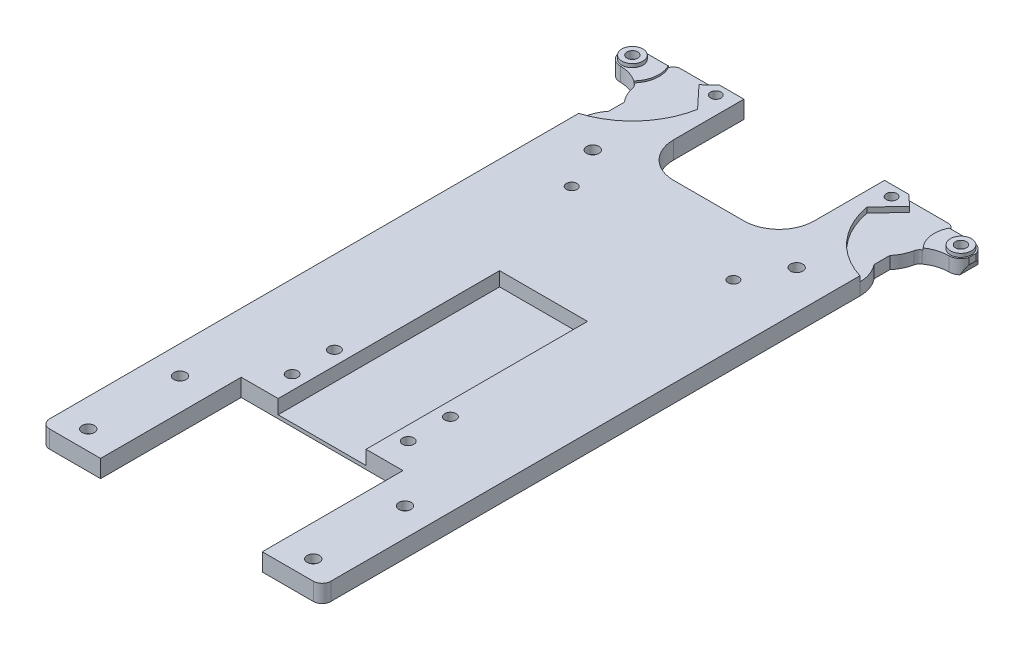
SolidWorks part; units mm, degrees
ref_plane "Front Plane" through (0, 0, 0) normal (0, 0, 1) x (1, 0, 0)
ref_plane "Top Plane" through (0, 0, 0) normal (0, 1, 0) x (1, 0, 0)
ref_plane "Right Plane" through (0, 0, 0) normal (1, 0, 0) x (0, 0, -1)
sketch "Sketch2" plane through (0, 0, 0) normal (0, 1, 0) x (1, 0, 0)
  line L0 (-93.7173, 35.2574) -> (6.2827, 35.2574)
  line L1 (6.2827, 35.2574) -> (6.2827, 25.2574)
  line L2 (6.2827, 25.2574) -> (-3.7173, 25.2574)
  line L3 (-3.7173, 25.2574) -> (-3.7173, -134.7426)
  line L4 (-3.7173, -134.7426) -> (6.2827, -134.7426)
  line L5 (6.2827, -134.7426) -> (6.2827, -144.7426)
  line L6 (6.2827, -144.7426) -> (-93.7173, -144.7426)
  line L7 (-93.7173, -144.7426) -> (-93.7173, -134.7426)
  line L8 (-93.7173, -134.7426) -> (-83.7173, -134.7426)
  line L9 (-83.7173, -134.7426) -> (-83.7173, 25.2574)
  line L10 (-83.7173, 25.2574) -> (-93.7173, 25.2574)
  line L11 (-93.7173, 25.2574) -> (-93.7173, 35.2574)
  line L12 (-43.7173, 35.2574) -> (-43.7173, -144.7426) construction
  line L13 (-83.7173, -54.7426) -> (-3.7173, -54.7426) construction
  circle A4 centre (-82.9402, 30.2574) radius 1.5
  circle A5 centre (-4.4944, 30.2574) radius 1.5
  circle A6 centre (-4.4944, -139.7426) radius 1.5
  circle A7 centre (-82.9402, -139.7426) radius 1.5
  circle A8 centre (-68.7173, 32.2574) radius 1.5
  circle A9 centre (-18.7173, 32.2574) radius 1.5
  circle A10 centre (-66.7173, -10.7426) radius 1.5
  circle A11 centre (-20.7173, -10.7426) radius 1.5
  dimension "D6" = 3
  dimension "D7" = 3
  dimension "D8" = 3
  dimension "D13" = 17
  dimension "D1" = 180
  dimension "D2" = 100
  dimension "D3" = 10
  dimension "D4" = 10
  dimension "D5" = 10
  dimension "D9" = 25
  dimension "D10" = 10
  dimension "D11" = 10.7771
  dimension "D12" = 5
  dimension "D14" = 46
extrude "Boss-Extrude1" add sketch "Sketch2" along normal blind 5
sketch "Sketch3" plane through (0, 5, 0) normal (0, 1, 0) x (1, 0, 0)
  line L0 (-93.7173, 35.2574) -> (-93.7173, 25.2574) construction
  line L1 (-93.7173, 33.6874) -> (-83.7173, 33.6874)
  line L2 (-93.7173, 33.6874) -> (-93.7173, 35.2574)
  line L3 (-93.7173, 35.2574) -> (-83.7173, 35.2574)
  line L4 (-83.7173, 33.6874) -> (-83.7173, 35.2574)
  line L5 (-88.7173, 35.2574) -> (-88.7173, 33.6874) construction
  line L6 (-93.7173, 34.4724) -> (-83.7173, 34.4724) construction
  line L7 (6.2827, 35.2574) -> (-93.7173, 35.2574) construction
  line L8 (-83.7173, 25.2574) -> (-83.7173, -134.7426) construction
  line L9 (-43.7173, 35.2574) -> (-43.7173, 20.5775) construction
  line L10 (6.2827, 35.2574) -> (-3.7173, 35.2574)
  line L11 (-3.7173, 33.6874) -> (-3.7173, 35.2574)
  line L12 (6.2827, 33.6874) -> (-3.7173, 33.6874)
  line L13 (6.2827, 33.6874) -> (6.2827, 35.2574)
  circle A0 centre (-82.9402, 30.2574) radius 1.5 construction
  point P404 (-88.7173, 34.4724)
  dimension "D1" = 3.43
extrude "Cut-Extrude1" cut sketch "Sketch3" against normal blind 10
fillet "Fillet1" radius 2 6 edges at (-93.7173, 2.5, -33.6874) (-83.7173, 2.5, -35.2574) (6.2827, 2.5, -25.2574) (6.2827, 2.5, -33.6874) (-3.7173, 2.5, -35.2574) (-93.7173, 2.5, -25.2574)
fillet "Fillet2" radius 2 8 edges at (-83.7173, 2.5, -25.2574) (-3.7173, 2.5, -25.2574) (-3.7173, 2.5, 134.7426) (-83.7173, 2.5, 134.7426) (-93.7173, 2.5, 134.7426) (-93.7173, 2.5, 144.7426) (6.2827, 2.5, 144.7426) (6.2827, 2.5, 134.7426)
sketch "Sketch30" plane through (0, 5, 0) normal (0, 1, 0) x (1, 0, 0)
  line L0 (-63.7173, 35.2574) -> (-63.7173, 5.2574)
  line L1 (-5.6705, 35.2574) -> (-81.7641, 35.2574) construction
  line L2 (-63.7173, 5.2574) -> (-23.7173, 5.2574)
  line L3 (-23.7173, 5.2574) -> (-23.7173, 35.2574)
  line L4 (-23.7173, 35.2574) -> (-63.7173, 35.2574)
  line L5 (-83.7173, 23.2574) -> (-83.7173, -132.7426) construction
  line L6 (-3.7173, -132.7426) -> (-3.7173, 23.2574) construction
  dimension "D1" = 40
  dimension "D2" = 20
  dimension "D3" = 30
  dimension "D4" = 20
extrude "Cut-Extrude6" cut sketch "Sketch30" against normal blind 10
sketch "Sketch34" plane through (0, 5, 0) normal (0, 1, 0) x (1, 0, 0)
  line L0 (-83.7173, -132.7426) -> (-83.7173, -144.7426)
  line L1 (-91.7173, -144.7426) -> (4.2827, -144.7426) construction
  line L2 (-96.6198, -144.7426) -> (-96.6198, -132.7426)
  line L3 (-96.6198, -132.7426) -> (-83.7173, -132.7426)
  line L4 (-96.6198, -144.7426) -> (-83.7173, -144.7426)
  line L5 (-43.7173, -144.7426) -> (-43.7173, -122.7477) construction
  line L6 (9.1852, -144.7426) -> (9.1852, -132.7426)
  line L7 (9.1852, -132.7426) -> (-3.7173, -132.7426)
  line L8 (-3.7173, -132.7426) -> (-3.7173, -144.7426)
  line L9 (9.1852, -144.7426) -> (-3.7173, -144.7426)
  line L10 (-83.7173, 23.2574) -> (-83.7173, -132.7426) construction
  dimension "D1" = 12.9025
extrude "Cut-Extrude9" cut sketch "Sketch34" against normal up to surface (5 mm away) up to face at (-43.7173, 0, 34.3905)
sketch "Sketch35" plane through (0, 5, 0) normal (0, 1, 0) x (1, 0, 0)
  line L0 (-83.7173, -144.7426) -> (-83.7173, -124.7426)
  line L1 (-83.7173, -144.7426) -> (-77.7173, -144.7426)
  line L2 (-83.7173, -124.7426) -> (-77.7173, -124.7426)
  line L3 (-77.7173, -144.7426) -> (-77.7173, -124.7426)
  line L4 (-83.7173, 23.2574) -> (-83.7173, -138.4596) construction
  line L5 (-3.7173, -144.7426) -> (-3.7173, -124.7426)
  line L6 (-3.7173, -144.7426) -> (-9.7173, -144.7426)
  line L7 (-3.7173, -124.7426) -> (-9.7173, -124.7426)
  line L8 (-9.7173, -144.7426) -> (-9.7173, -124.7426)
  line L9 (-3.7173, -138.4596) -> (-3.7173, 23.2574) construction
  dimension "D1" = 6
  dimension "D2" = 20
  dimension "D3" = 6
  dimension "D4" = 20
extrude "Boss-Extrude10" add sketch "Sketch35" against normal up to surface (5 mm away) up to face at (-43.7173, 0, 11.3543)
fillet "Fillet4" radius 2.5 2 edges at (-3.7173, 2.5, 144.7426) (-83.7173, 2.5, 144.7426)
fillet "Fillet6" radius 10 2 edges at (-63.7173, 2.5, -5.2574) (-23.7173, 2.5, -5.2574)
sketch "Sketch37" plane through (0, 5, 0) normal (0, 1, 0) x (1, 0, 0)
  line L0 (-81.2173, -144.7426) -> (-6.2173, -144.7426) construction
  line L1 (-66.7173, -144.7426) -> (-20.7173, -144.7426)
  line L2 (-66.7173, -144.7426) -> (-66.7173, -104.7426)
  line L3 (-66.7173, -104.7426) -> (-20.7173, -104.7426)
  line L4 (-20.7173, -144.7426) -> (-20.7173, -104.7426)
  line L5 (-3.7173, -142.2426) -> (-3.7173, 23.2574) construction
  line L6 (-83.7173, 23.2574) -> (-83.7173, -142.2426) construction
  dimension "D1" = 40
  dimension "D2" = 17
  dimension "D3" = 17
extrude "Cut-Extrude10" cut sketch "Sketch37" against normal blind 10
sketch "Sketch38" plane through (0, 5, 0) normal (0, 1, 0) x (1, 0, 0)
  line L0 (-83.7173, -99.7426) -> (-3.7173, -99.7426) construction
  line L1 (-83.7173, 23.2574) -> (-83.7173, -142.2426) construction
  line L2 (-3.7173, -142.2426) -> (-3.7173, 23.2574) construction
  line L3 (-20.7173, -144.7426) -> (-6.2173, -144.7426) construction
  line L4 (-43.7173, -99.7426) -> (-43.7173, -22.3718) construction
  line L5 (-4.4944, 30.2574) -> (-43.7173, -99.7426) construction
  line L6 (-43.7173, -99.7426) -> (-82.9402, 30.2574) construction
  line L7 (-3.7173, -124.7426) -> (-83.7173, -124.7426) construction
  line L8 (-43.7173, -124.7426) -> (-43.7173, -111.0267) construction
  line L9 (-43.7173, -124.7426) -> (3.015, 30.2574) construction
  line L10 (-43.7173, -124.7426) -> (-90.4496, 30.2574) construction
  circle A0 centre (3.015, 30.2574) radius 1.55
  circle A1 centre (-90.4496, 30.2574) radius 1.55
  point P8 (-43.7173, -99.7426)
  dimension "D7" = 3.1
  dimension "D8" = 3.1
  dimension "D1" = 45
  dimension "D2" = 16.789
  dimension "D3" = 16.789
  dimension "D4" = 20
  dimension "D5" = 16.778
  dimension "D6" = 16.778
extrude "Cut-Extrude11" cut sketch "Sketch38" against normal blind 10
sketch "Sketch39" plane through (0, 5, 0) normal (0, 1, 0) x (1, 0, 0)
  line L1 (-84.6764, 28.5195) -> (-81.2041, 28.5195)
  line L2 (-84.6764, 28.5195) -> (-84.6764, 31.9953)
  line L3 (-84.6764, 31.9953) -> (-81.2041, 31.9953)
  line L4 (-81.2041, 28.5195) -> (-81.2041, 31.9953)
  line L5 (-84.6764, 28.5195) -> (-81.2041, 31.9953) construction
  line L6 (-84.6764, 31.9953) -> (-81.2041, 28.5195) construction
  line L7 (-6.4892, 28.105) -> (-2.4995, 28.105)
  line L8 (-6.4892, 28.105) -> (-6.4892, 32.4097)
  line L9 (-6.4892, 32.4097) -> (-2.4995, 32.4097)
  line L10 (-2.4995, 28.105) -> (-2.4995, 32.4097)
  line L11 (-6.4892, 28.105) -> (-2.4995, 32.4097) construction
  line L12 (-6.4892, 32.4097) -> (-2.4995, 28.105) construction
  point P0 (-82.9402, 30.2574)
  point P6 (-4.4944, 30.2574)
extrude "Boss-Extrude11" add sketch "Sketch39" against normal up to surface (5 mm away) up to face at (-90.4496, 0, -31.8074)
sketch "Sketch40" plane through (0, 5, 0) normal (0, 1, 0) x (1, 0, 0)
  line L0 (-20.7173, -104.7426) -> (-66.7173, -104.7426) construction
  line L1 (-56.2173, -104.7426) -> (-31.2173, -104.7426)
  line L2 (-56.2173, -104.7426) -> (-56.2173, -41.7426)
  line L3 (-56.2173, -41.7426) -> (-31.2173, -41.7426)
  line L4 (-31.2173, -104.7426) -> (-31.2173, -41.7426)
  line L5 (-20.7173, -144.7426) -> (-20.7173, -104.7426) construction
  dimension "D1" = 25
  dimension "D2" = 10.5
  dimension "D3" = 63
extrude "Cut-Extrude12" cut sketch "Sketch40" against normal blind 4
sketch "Sketch41" plane through (0, 0, 0) normal (0, -1, 0) x (1, 0, 0)
  line L0 (-20.7173, 144.7426) -> (-6.2173, 144.7426) construction
  line L1 (-3.7173, 142.2426) -> (-3.7173, -23.2574) construction
  line L2 (-43.7173, 104.7426) -> (-43.7173, 173.7336) construction
  line L3 (-66.7173, 104.7426) -> (-20.7173, 104.7426) construction
  line L4 (-83.7173, -23.2574) -> (-83.7173, 142.2426) construction
  line L5 (-63.7173, -35.2574) -> (-81.7641, -35.2574) construction
  circle A0 centre (-11.7173, 139.2426) radius 1.75
  circle A1 centre (-11.7173, 113.1526) radius 1.75
  circle A2 centre (-75.7173, 139.2426) radius 1.75
  circle A3 centre (-75.7173, 113.1526) radius 1.75
  circle A4 centre (-72.7173, -1.2574) radius 1.75
  circle A5 centre (-14.7173, -1.2574) radius 1.75
  dimension "D1" = 3.5
  dimension "D3" = 8
  dimension "D4" = 3.5
  dimension "D7" = 3.5
  dimension "D2" = 5.5
  dimension "D5" = 8
  dimension "D6" = 26.09
  dimension "D8" = 11
  dimension "D9" = 34
extrude "Cut-Extrude13" cut sketch "Sketch41" against normal blind 10
sketch "Sketch42" plane through (0, 0, 0) normal (0, -1, 0) x (-1, 0, 0)
  line L0 (-4.2827, 33.6874) -> (3.7173, 33.6874) construction
  line L1 (3.0958, 24.7064) -> (-10.5926, 24.9306)
  line L2 (-10.5926, 24.9306) -> (-9.0481, 35.5793)
  line L3 (-9.0481, 35.5793) -> (-3.015, 33.6874)
  line L4 (43.7173, 5.2574) -> (43.7173, -10.2326) construction
  line L5 (33.7173, 5.2574) -> (53.7173, 5.2574) construction
  line L6 (98.0272, 24.9306) -> (96.4827, 35.5793)
  line L7 (84.3388, 24.7064) -> (98.0272, 24.9306)
  line L8 (96.4827, 35.5793) -> (90.4496, 33.6874)
  line L9 (3.7173, -142.2426) -> (3.7173, 23.2574) construction
  line L10 (1.4769, 19.0161) -> (5.9576, 19.0161)
  line L11 (1.4769, 19.0161) -> (1.4769, 14.5172)
  line L12 (1.4769, 14.5172) -> (5.9576, 14.5172)
  line L13 (5.9576, 19.0161) -> (5.9576, 14.5172)
  line L14 (1.4769, 19.0161) -> (5.9576, 14.5172) construction
  line L15 (1.4769, 14.5172) -> (5.9576, 19.0161) construction
  line L16 (85.9576, 14.5172) -> (81.4769, 14.5172)
  line L17 (81.4769, 19.0161) -> (81.4769, 14.5172)
  line L18 (85.9576, 19.0161) -> (81.4769, 19.0161)
  line L19 (85.9576, 19.0161) -> (85.9576, 14.5172)
  arc A0 (-3.015, 33.6874) -> (-3.015, 26.8274) centre (-3.015, 30.2574) ccw
  arc A1 (-3.015, 26.8274) -> (3.0958, 24.7064) centre (-3.015, 16.9637) cw
  arc A2 (3.7173, 23.2574) -> (1.7173, 25.2574) centre (1.7173, 23.2574) ccw construction
  arc A3 (90.4496, 26.8274) -> (84.3388, 24.7064) centre (90.4496, 16.9637) ccw
  arc A4 (90.4496, 33.6874) -> (90.4496, 26.8274) centre (90.4496, 30.2574) cw
  point P24 (3.7173, 16.7666)
extrude "Cut-Extrude14" cut sketch "Sketch42" against normal blind 10
fillet "Fillet7" radius 10 7 edges at (-3.7173, 2.5, -23.2574) (-3.7173, 2.5, -19.0161) (-3.7173, 2.5, -14.5172) (-4.8375, 5, -14.5172) (-4.8375, 5, -19.0161) (-4.8375, 0, -19.0161) (-4.8375, 0, -14.5172)
fillet "Fillet8" radius 10 7 edges at (-83.7173, 2.5, -23.2574) (-83.7173, 2.5, -19.0161) (-83.7173, 2.5, -14.5172) (-82.5971, 5, -14.5172) (-82.5971, 5, -19.0161) (-82.5971, 0, -19.0161) (-82.5971, 0, -14.5172)
sketch "Sketch43" plane through (0, 5, 0) normal (0, 1, 0) x (1, 0, 0)
  line L0 (-31.2173, -104.7426) -> (-31.2173, -41.7426) construction
  line L1 (-20.7173, -104.7426) -> (-31.2173, -104.7426) construction
  line L2 (-43.7173, -104.7426) -> (-43.7173, -93.2814) construction
  line L3 (-56.2173, -104.7426) -> (-31.2173, -104.7426) construction
  circle A0 centre (-27.2173, -96.7426) radius 1.6
  circle A1 centre (-27.2173, -84.7426) radius 1.6
  circle A2 centre (-60.2173, -96.7426) radius 1.6
  circle A3 centre (-60.2173, -84.7426) radius 1.6
  dimension "D1" = 3.2
  dimension "D3" = 3.2
  dimension "D2" = 4
  dimension "D4" = 20
  dimension "D5" = 12
extrude "Cut-Extrude15" cut sketch "Sketch43" against normal blind 10
sketch "Sketch44" plane through (0, 0, 0) normal (0, -1, 0) x (1, 0, 0)
  line L0 (-43.7173, 104.7426) -> (-43.7173, 122.314) construction
  line L1 (-72.4264, 139.2426) -> (-74.0718, 142.0926)
  line L2 (-74.0718, 142.0926) -> (-77.3627, 142.0926)
  line L3 (-77.3627, 142.0926) -> (-79.0082, 139.2426)
  line L4 (-79.0082, 139.2426) -> (-77.3627, 136.3926)
  line L5 (-77.3627, 136.3926) -> (-74.0718, 136.3926)
  line L6 (-74.0718, 136.3926) -> (-72.4264, 139.2426)
  line L7 (-72.4264, 113.1526) -> (-74.0718, 116.0026)
  line L8 (-74.0718, 116.0026) -> (-77.3627, 116.0026)
  line L9 (-77.3627, 116.0026) -> (-79.0082, 113.1526)
  line L10 (-79.0082, 113.1526) -> (-77.3627, 110.3026)
  line L11 (-77.3627, 110.3026) -> (-74.0718, 110.3026)
  line L12 (-74.0718, 110.3026) -> (-72.4264, 113.1526)
  line L13 (-56.9264, 96.7426) -> (-58.5718, 99.5926)
  line L14 (-58.5718, 99.5926) -> (-61.8627, 99.5926)
  line L15 (-61.8627, 99.5926) -> (-63.5082, 96.7426)
  line L16 (-63.5082, 96.7426) -> (-61.8627, 93.8926)
  line L17 (-61.8627, 93.8926) -> (-58.5718, 93.8926)
  line L18 (-58.5718, 93.8926) -> (-56.9264, 96.7426)
  line L19 (-56.9264, 84.7426) -> (-58.5718, 87.5926)
  line L20 (-58.5718, 87.5926) -> (-61.8627, 87.5926)
  line L21 (-61.8627, 87.5926) -> (-63.5082, 84.7426)
  line L22 (-63.5082, 84.7426) -> (-61.8627, 81.8926)
  line L23 (-61.8627, 81.8926) -> (-58.5718, 81.8926)
  line L24 (-58.5718, 81.8926) -> (-56.9264, 84.7426)
  line L31 (-69.4264, -1.2574) -> (-71.0718, 1.5926)
  line L32 (-71.0718, 1.5926) -> (-74.3627, 1.5926)
  line L33 (-74.3627, 1.5926) -> (-76.0082, -1.2574)
  line L34 (-76.0082, -1.2574) -> (-74.3627, -4.1074)
  line L35 (-74.3627, -4.1074) -> (-71.0718, -4.1074)
  line L36 (-71.0718, -4.1074) -> (-69.4264, -1.2574)
  line L37 (-65.4264, -32.2574) -> (-67.0718, -29.4074)
  line L38 (-67.0718, -29.4074) -> (-70.3627, -29.4074)
  line L39 (-70.3627, -29.4074) -> (-72.0082, -32.2574)
  line L40 (-72.0082, -32.2574) -> (-70.3627, -35.1074)
  line L41 (-70.3627, -35.1074) -> (-67.0718, -35.1074)
  line L42 (-67.0718, -35.1074) -> (-65.4264, -32.2574)
  line L49 (-66.7173, 104.7426) -> (-20.7173, 104.7426) construction
  line L56 (-20.3627, -35.1074) -> (-22.0082, -32.2574)
  line L57 (-17.0718, -35.1074) -> (-20.3627, -35.1074)
  line L58 (-15.4264, -32.2574) -> (-17.0718, -35.1074)
  line L59 (-17.0718, -29.4074) -> (-15.4264, -32.2574)
  line L60 (-20.3627, -29.4074) -> (-17.0718, -29.4074)
  line L61 (-22.0082, -32.2574) -> (-20.3627, -29.4074)
  line L62 (-16.3627, -4.1074) -> (-18.0082, -1.2574)
  line L63 (-13.0718, -4.1074) -> (-16.3627, -4.1074)
  line L64 (-11.4264, -1.2574) -> (-13.0718, -4.1074)
  line L65 (-13.0718, 1.5926) -> (-11.4264, -1.2574)
  line L66 (-16.3627, 1.5926) -> (-13.0718, 1.5926)
  line L67 (-18.0082, -1.2574) -> (-16.3627, 1.5926)
  line L74 (-28.8627, 81.8926) -> (-30.5082, 84.7426)
  line L75 (-25.5718, 81.8926) -> (-28.8627, 81.8926)
  line L76 (-23.9264, 84.7426) -> (-25.5718, 81.8926)
  line L77 (-25.5718, 87.5926) -> (-23.9264, 84.7426)
  line L78 (-28.8627, 87.5926) -> (-25.5718, 87.5926)
  line L79 (-30.5082, 84.7426) -> (-28.8627, 87.5926)
  line L80 (-28.8627, 93.8926) -> (-30.5082, 96.7426)
  line L81 (-25.5718, 93.8926) -> (-28.8627, 93.8926)
  line L82 (-23.9264, 96.7426) -> (-25.5718, 93.8926)
  line L83 (-25.5718, 99.5926) -> (-23.9264, 96.7426)
  line L84 (-28.8627, 99.5926) -> (-25.5718, 99.5926)
  line L85 (-30.5082, 96.7426) -> (-28.8627, 99.5926)
  line L86 (-13.3627, 110.3026) -> (-15.0082, 113.1526)
  line L87 (-10.0718, 110.3026) -> (-13.3627, 110.3026)
  line L88 (-8.4264, 113.1526) -> (-10.0718, 110.3026)
  line L89 (-10.0718, 116.0026) -> (-8.4264, 113.1526)
  line L90 (-13.3627, 116.0026) -> (-10.0718, 116.0026)
  line L91 (-15.0082, 113.1526) -> (-13.3627, 116.0026)
  line L92 (-13.3627, 136.3926) -> (-15.0082, 139.2426)
  line L93 (-10.0718, 136.3926) -> (-13.3627, 136.3926)
  line L94 (-8.4264, 139.2426) -> (-10.0718, 136.3926)
  line L95 (-10.0718, 142.0926) -> (-8.4264, 139.2426)
  line L96 (-13.3627, 142.0926) -> (-10.0718, 142.0926)
  line L97 (-15.0082, 139.2426) -> (-13.3627, 142.0926)
  circle A0 centre (-75.7173, 139.2426) radius 2.85 construction
  circle A1 centre (-75.7173, 113.1526) radius 2.85 construction
  circle A2 centre (-60.2173, 96.7426) radius 2.85 construction
  circle A3 centre (-60.2173, 84.7426) radius 2.85 construction
  circle A5 centre (-72.7173, -1.2574) radius 2.85 construction
  circle A6 centre (-68.7173, -32.2574) radius 2.85 construction
  circle A8 centre (3.015, -30.2574) radius 2.85 construction
  circle A9 centre (-18.7173, -32.2574) radius 2.85 construction
  circle A10 centre (-14.7173, -1.2574) radius 2.85 construction
  circle A12 centre (-27.2173, 84.7426) radius 2.85 construction
  circle A13 centre (-27.2173, 96.7426) radius 2.85 construction
  circle A14 centre (-11.7173, 113.1526) radius 2.85 construction
  circle A15 centre (-11.7173, 139.2426) radius 2.85 construction
  dimension "D1" = 5.7
  dimension "D2" = 5.7
  dimension "D3" = 5.7
  dimension "D4" = 5.7
  dimension "D6" = 5.7
  dimension "D7" = 5.7
extrude "Cut-Extrude16" cut sketch "Sketch44" against normal blind 2.6
sketch "Sketch45" plane through (0, 5, 0) normal (0, 1, 0) x (1, 0, 0)
  line L0 (-43.7173, 5.2574) -> (-43.7173, 61.3932) construction
  line L1 (-53.7173, 5.2574) -> (-33.7173, 5.2574) construction
  circle A0 centre (-90.4496, 30.2574) radius 7.55
  circle A1 centre (-90.4496, 30.2574) radius 16.8242
  circle A2 centre (3.015, 30.2574) radius 7.55
  circle A3 centre (3.015, 30.2574) radius 16.8242
  circle A4 centre (3.015, 30.2574) radius 1.55 construction
  circle A5 centre (-68.7173, 32.2574) radius 1.5 construction
  dimension "D1" = 3.5
  dimension "D2" = 6
extrude "Cut-Extrude17" cut sketch "Sketch45" against normal blind 1
sketch "Sketch46" plane through (0, 4, 0) normal (0, 1, 0) x (1, 0, 0)
  line L0 (-67.8089, 26.1519) -> (-73.664, 32.4296)
  line L1 (-73.664, 32.4296) -> (-68.5206, 37.2269)
  line L2 (-43.7173, 5.2574) -> (-43.7173, 37.2269) construction
  line L3 (-53.7173, 5.2574) -> (-33.7173, 5.2574) construction
  line L4 (-13.7705, 32.4296) -> (-18.914, 37.2269)
  line L5 (-19.6257, 26.1519) -> (-13.7705, 32.4296)
  arc A0 (-68.5206, 37.2269) -> (-67.8089, 26.1519) centre (-90.4496, 30.2574) ccw
  circle A1 centre (-68.7173, 32.2574) radius 1.5 construction
  circle A2 centre (-90.4496, 30.2574) radius 7.6023
  circle A3 centre (3.015, 30.2574) radius 7.6023
  arc A4 (-18.914, 37.2269) -> (-19.6257, 26.1519) centre (3.015, 30.2574) cw
  dimension "D1" = 3.5
  dimension "D2" = 3.5
extrude "Cut-Extrude18" cut sketch "Sketch46" against normal blind 0.5 and the other way blind 1
sketch "Sketch48" plane through (0, 5, 0) normal (0, 1, 0) x (1, 0, 0)
  circle A0 centre (-90.4496, 30.2574) radius 3
  circle A1 centre (3.015, 30.2574) radius 3
  circle A2 centre (-90.4496, 30.2574) radius 10
  circle A3 centre (3.015, 30.2574) radius 10
  dimension "D1" = 6
  dimension "D2" = 6
  dimension "D3" = 20
  dimension "D4" = 20
extrude "Cut-Extrude19" cut sketch "Sketch48" against normal blind 1 contours A2
ref_plane "Plane1" through (-43.7173, 0, 0) normal (-1, 0, 0) x (0, 0, 1)
other "SurfaceCut1" flip cut yes
chamfer "Chamfer2" distance 1 angle 65 1 edges at (6.2827, 0, -30.2574) first distance on face at (-20.7173, 0, 9.2426)
sketch "Sketch49" plane through (0, 0, 0) normal (0, -1, 0) x (1, 0, 0)
  circle A0 centre (3.015, -30.2574) radius 1.55
extrude "Boss-Extrude13" add sketch "Sketch49" against normal blind 3
ref_plane "Plane2" through (3.0127, 0, 0) normal (1, 0, 0) x (0, 0, -1)
sketch "Sketch50" plane through (3.0127, 0, 0) normal (1, 0, 0) x (0, 0, -1)
  line L0 (30.2574, 3) -> (30.2574, 1)
  line L1 (31.8074, 3) -> (28.7074, 3) construction
  line L3 (31.8074, 3) -> (30.2574, 3)
  line L4 (30.2574, 1) -> (31.7074, 1)
  line L5 (31.7074, 1) -> (31.8074, 3)
  line L6 (32.2574, 0) -> (29.4074, 0) construction
  dimension "D1" = 1.45
  dimension "D2" = 1.55
  dimension "D3" = 1
revolve "Cut-Revolve1" cut sketch "Sketch50" angle 360 about L0
mirror "Mirror1" about plane through (-43.7173, 0, 0) normal (-1, 0, 0) of bodies 144
